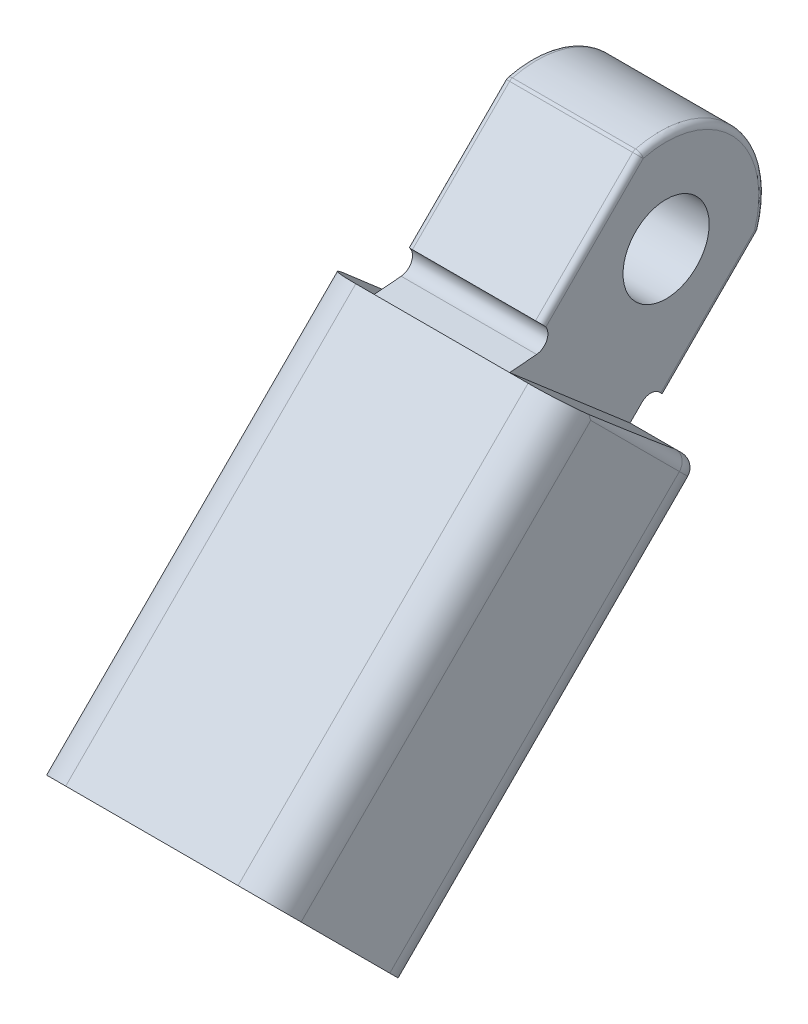
SolidWorks part; units mm, degrees
material "ABS"
ref_plane "Alzado" through (0, 0, 0) normal (0, 0, 1) x (1, 0, 0)
ref_plane "Planta" through (0, 0, 0) normal (0, 1, 0) x (1, 0, 0)
ref_plane "Vista lateral" through (0, 0, 0) normal (1, 0, 0) x (0, 0, -1)
sketch "Croquis1" plane through (0, 0, 0) normal (1, 0, 0) x (0, 0, -1)
  line L0 (267.7914, 425.6228) -> (162.5455, 393.6335) construction
  line L1 (126.6392, 368.127) -> (138.0825, 356.6837)
  line L2 (138.0825, 356.6837) -> (162.3173, 380.9185)
  line L3 (162.3173, 380.9185) -> (159.9826, 383.2532)
  line L4 (159.9826, 383.2532) -> (161.6596, 384.9302)
  line L5 (161.6596, 384.9302) -> (162.8269, 383.7629)
  line L6 (162.8269, 383.7629) -> (170.53, 391.4659)
  line L7 (126.6392, 368.127) -> (150.1999, 391.6877)
  line L8 (150.1999, 391.6877) -> (154.5376, 392.0522)
  line L9 (154.5376, 392.0522) -> (152.8035, 393.7863)
  line L10 (152.8035, 393.7863) -> (160.7929, 401.7758)
  circle A0 centre (162.9097, 394.022) radius 3.5
  arc A1 (160.7929, 401.7758) -> (170.53, 391.4659) centre (162.9097, 394.022) cw
  dimension "D2" = 7
  dimension "D1" = 110
extrude "Saliente-Extruir1" add sketch "Croquis1" along normal blind 20
sketch "Croquis2" plane through (20, 0, 0) normal (1, 0, 0) x (0, 0, -1)
  line L0 (150.1999, 391.6877) -> (159.9826, 383.2532)
  line L10 (150.1999, 391.6877) -> (126.6392, 368.127)
  line L11 (126.6392, 368.127) -> (138.0825, 356.6837)
  line L12 (138.0825, 356.6837) -> (162.3173, 380.9185)
  line L13 (162.3173, 380.9185) -> (159.9826, 383.2532)
  line L14 (159.9826, 383.2532) -> (161.6596, 384.9302)
  line L15 (161.6596, 384.9302) -> (162.8269, 383.7629)
  line L16 (162.8269, 383.7629) -> (170.53, 391.4659)
  line L17 (160.7929, 401.7758) -> (152.8035, 393.7863)
  line L18 (152.8035, 393.7863) -> (154.5376, 392.0522)
  line L19 (154.5376, 392.0522) -> (150.1999, 391.6877)
  line L20 (150.1999, 391.6877) -> (126.6392, 368.127)
  line L21 (126.6392, 368.127) -> (138.0825, 356.6837)
  line L22 (138.0825, 356.6837) -> (162.3173, 380.9185)
  line L23 (162.3173, 380.9185) -> (159.9826, 383.2532)
  line L24 (159.9826, 383.2532) -> (161.6596, 384.9302)
  line L25 (161.6596, 384.9302) -> (162.8269, 383.7629)
  line L26 (162.8269, 383.7629) -> (170.53, 391.4659)
  line L27 (160.7929, 401.7758) -> (152.8035, 393.7863)
  line L28 (152.8035, 393.7863) -> (154.5376, 392.0522)
  line L29 (154.5376, 392.0522) -> (150.1999, 391.6877)
  arc A1 (170.53, 391.4659) -> (160.7929, 401.7758) centre (162.9097, 394.022) ccw
  arc A2 (170.53, 391.4659) -> (160.7929, 401.7758) centre (162.9097, 394.022) ccw
  line M16 (159.9826, 383.2532) -> (161.6596, 384.9302)
  line M17 (161.6596, 384.9302) -> (162.8269, 383.7629)
  line M18 (162.8269, 383.7629) -> (170.53, 391.4659)
  arc M19 (170.53, 391.4659) -> (160.7929, 401.7758) centre (162.9097, 394.022) ccw
  line M20 (160.7929, 401.7758) -> (152.8035, 393.7863)
  line M21 (152.8035, 393.7863) -> (154.5376, 392.0522)
  line M22 (154.5376, 392.0522) -> (150.1999, 391.6877)
  circle M23 centre (162.9097, 394.022) radius 3.5
  dimension "D1" = 0
extrude "Cortar-Extruir1" cut sketch "Croquis2" against normal blind 4.5 contours L0 M22 M16 M17 M18 M19 M20 M21 M23 region at (20, 391.5909, -152.3922)
sketch "Croquis3" plane through (0, 0, 0) normal (-1, 0, 0) x (0, 0, 1)
  line L0 (-159.9826, 383.2532) -> (-150.1999, 391.6877)
  line L10 (-126.6392, 368.127) -> (-150.1999, 391.6877)
  line L11 (-150.1999, 391.6877) -> (-154.5376, 392.0522)
  line L12 (-154.5376, 392.0522) -> (-152.8035, 393.7863)
  line L13 (-152.8035, 393.7863) -> (-160.7929, 401.7758)
  line L14 (-170.53, 391.4659) -> (-162.8269, 383.7629)
  line L15 (-162.8269, 383.7629) -> (-161.6596, 384.9302)
  line L16 (-161.6596, 384.9302) -> (-159.9826, 383.2532)
  line L17 (-159.9826, 383.2532) -> (-162.3173, 380.9185)
  line L18 (-162.3173, 380.9185) -> (-138.0825, 356.6837)
  line L19 (-138.0825, 356.6837) -> (-126.6392, 368.127)
  line L20 (-126.6392, 368.127) -> (-150.1999, 391.6877)
  line L21 (-150.1999, 391.6877) -> (-154.5376, 392.0522)
  line L22 (-154.5376, 392.0522) -> (-152.8035, 393.7863)
  line L23 (-152.8035, 393.7863) -> (-160.7929, 401.7758)
  line L24 (-170.53, 391.4659) -> (-162.8269, 383.7629)
  line L25 (-162.8269, 383.7629) -> (-161.6596, 384.9302)
  line L26 (-161.6596, 384.9302) -> (-159.9826, 383.2532)
  line L27 (-159.9826, 383.2532) -> (-162.3173, 380.9185)
  line L28 (-162.3173, 380.9185) -> (-138.0825, 356.6837)
  line L29 (-138.0825, 356.6837) -> (-126.6392, 368.127)
  arc A1 (-160.7929, 401.7758) -> (-170.53, 391.4659) centre (-162.9097, 394.022) ccw
  arc A2 (-160.7929, 401.7758) -> (-170.53, 391.4659) centre (-162.9097, 394.022) ccw
  line M13 (-150.1999, 391.6877) -> (-154.5376, 392.0522)
  line M14 (-154.5376, 392.0522) -> (-152.8035, 393.7863)
  line M15 (-152.8035, 393.7863) -> (-160.7929, 401.7758)
  arc M16 (-160.7929, 401.7758) -> (-170.53, 391.4659) centre (-162.9097, 394.022) ccw
  line M17 (-170.53, 391.4659) -> (-162.8269, 383.7629)
  line M18 (-162.8269, 383.7629) -> (-161.6596, 384.9302)
  line M19 (-161.6596, 384.9302) -> (-159.9826, 383.2532)
  circle M23 centre (-162.9097, 394.022) radius 3.5
  dimension "D1" = 0
extrude "Cortar-Extruir2" cut sketch "Croquis3" against normal blind 4.5 contours L0 M19 M13 M14 M15 M16 M17 M18 M23 region at (0, 384.2897, -160.6231)
fillet "Redondeo1" radius 3 4 edges at (0, 368.8011, -150.1999) (20, 368.8011, -150.1999) (0, 379.9073, -138.4195) (20, 379.9073, -138.4195)
fillet "Redondeo2" radius 1 5 edges at (20, 383.1465, -160.0893) (19.1213, 381.5398, -161.6959) (0, 383.1465, -160.0893) (0.8787, 381.5398, -161.6959) (10, 380.9185, -162.3173)
fillet "Redondeo3" radius 0.5 8 edges at (4.5, 387.6144, -166.6785) (4.5, 397.781, -156.7982) (15.5, 397.781, -156.7982) (15.5, 387.6144, -166.6785) (10, 391.4659, -170.53) (10, 401.7758, -160.7929) (4.5, 399.5407, -168.7531) (15.5, 399.5407, -168.7531)
fillet "Redondeo4" radius 1 2 edges at (10, 384.9302, -161.6596) (10, 392.0522, -154.5376)
sketch "Croquis4" plane through (0, 247.3831, -247.3831) normal (0, -0.7071, 0.7071) x (1, 0, 0)
  line L0 (10, 170.7577) -> (10, 154.5744) construction
  line L2 (17, 170.7577) -> (3, 170.7577) construction
  line L4 (17, 154.5744) -> (3, 154.5744) construction
  line L6 (6.25, 168.916) -> (13.75, 168.916)
  line L7 (4.75, 167.416) -> (4.75, 157.916)
  line L8 (6.25, 156.416) -> (13.75, 156.416)
  line L9 (15.25, 167.416) -> (15.25, 157.916)
  line L10 (4.75, 168.916) -> (15.25, 156.416) construction
  line L11 (4.75, 156.416) -> (15.25, 168.916) construction
  arc A0 (13.75, 168.916) -> (15.25, 167.416) centre (13.75, 167.416) cw
  arc A1 (13.75, 156.416) -> (15.25, 157.916) centre (13.75, 157.916) ccw
  arc A2 (4.75, 157.916) -> (6.25, 156.416) centre (6.25, 157.916) ccw
  arc A3 (6.25, 168.916) -> (4.75, 167.416) centre (6.25, 167.416) ccw
  point P6 (10, 162.666)
  dimension "D3" = 1.5
  dimension "D4" = 1.5
  dimension "D5" = 1.5
  dimension "D6" = 1.5
  dimension "D1" = 12.5
  dimension "D2" = 10.5
extrude "Cortar-Extruir3" cut sketch "Croquis4" against normal blind 20
